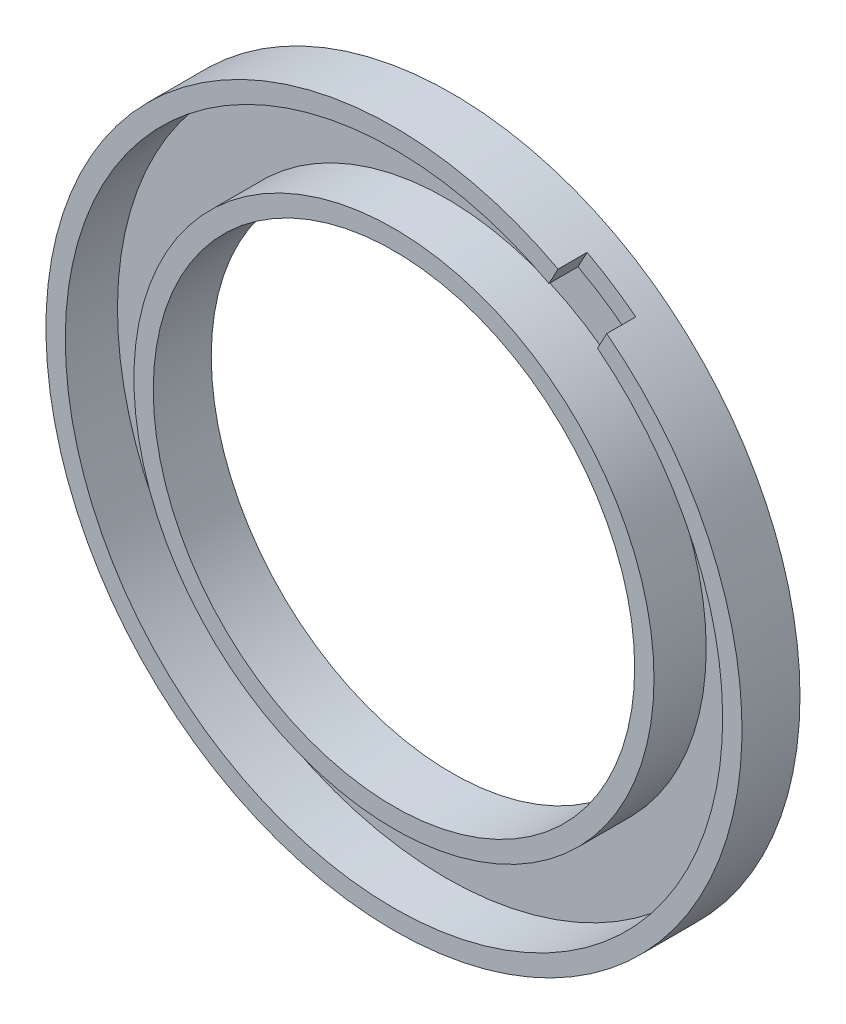
SolidWorks part; units mm, degrees
ref_plane "Front Plane" through (0, 0, 0) normal (0, 0, 1) x (1, 0, 0)
ref_plane "Top Plane" through (0, 0, 0) normal (0, 1, 0) x (1, 0, 0)
ref_plane "Right Plane" through (0, 0, 0) normal (1, 0, 0) x (0, 0, -1)
sketch "Sketch1" plane through (0, 0, 0) normal (0, 0, 1) x (1, 0, 0)
  circle A0 centre (0, 0) radius 36
  circle A1 centre (0, 0) radius 34
  circle A2 centre (0, 0) radius 26.9
  circle A3 centre (0, 0) radius 24.9
  point P5 (36, 0)
  point P6 (34, 0)
  point P7 (26.9, 0)
  point P8 (-26.9, 0)
  point P9 (-36, 0)
  point P10 (-34, 0)
  point P11 (24.9, 0)
  dimension "D1" = 2
  dimension "D2" = 68
  dimension "D3" = 7.1
  dimension "D4" = 2
extrude "Boss-Extrude1" add sketch "Sketch1" along normal blind 6 contours A0 A1 | A2 A3 region at (-34.9818, 0, 0) region at (-26.1392, 0, 0)
extrude "Boss-Extrude2" add sketch "Sketch1<3>" along normal blind 0.6 contours A1 A2 region at (-33.0383, 0, 0)
sketch "Sketch1<3>" plane through (0, 0, 0) normal (0, 0, 1) x (1, 0, 0) same geometry as "Sketch1"
sketch "Sketch4" plane through (0, 0, 6) normal (0, 0, 1) x (1, 0, 0)
  line L0 (22.0151, 28.4839) -> (21.0558, 26.6956)
  line L1 (16.0353, 29.9811) -> (16.9786, 31.7447)
  line L2 (16.9786, 31.7447) -> (21.0558, 32.2577)
  line L3 (21.0558, 32.2577) -> (22.0151, 28.4839)
  line L4 (16.0353, 29.9811) -> (17.2877, 26.9857)
  line L5 (17.2877, 26.9857) -> (21.0558, 26.6956)
  circle A0 centre (0, 0) radius 36 construction
  circle A1 centre (0, 0) radius 34 construction
  circle A2 centre (0, 0) radius 34 construction
  dimension "D1" = 6
  dimension "D2" = 6
  dimension "D3" = 31.7447
  dimension "D4" = 29.9811
  dimension "D5" = 4.0772
  dimension "D6" = 3.7738
  dimension "D7" = 2.9954
  dimension "D8" = 3.768
extrude "Cut-Extrude1" cut sketch "Sketch4" against normal blind 3
